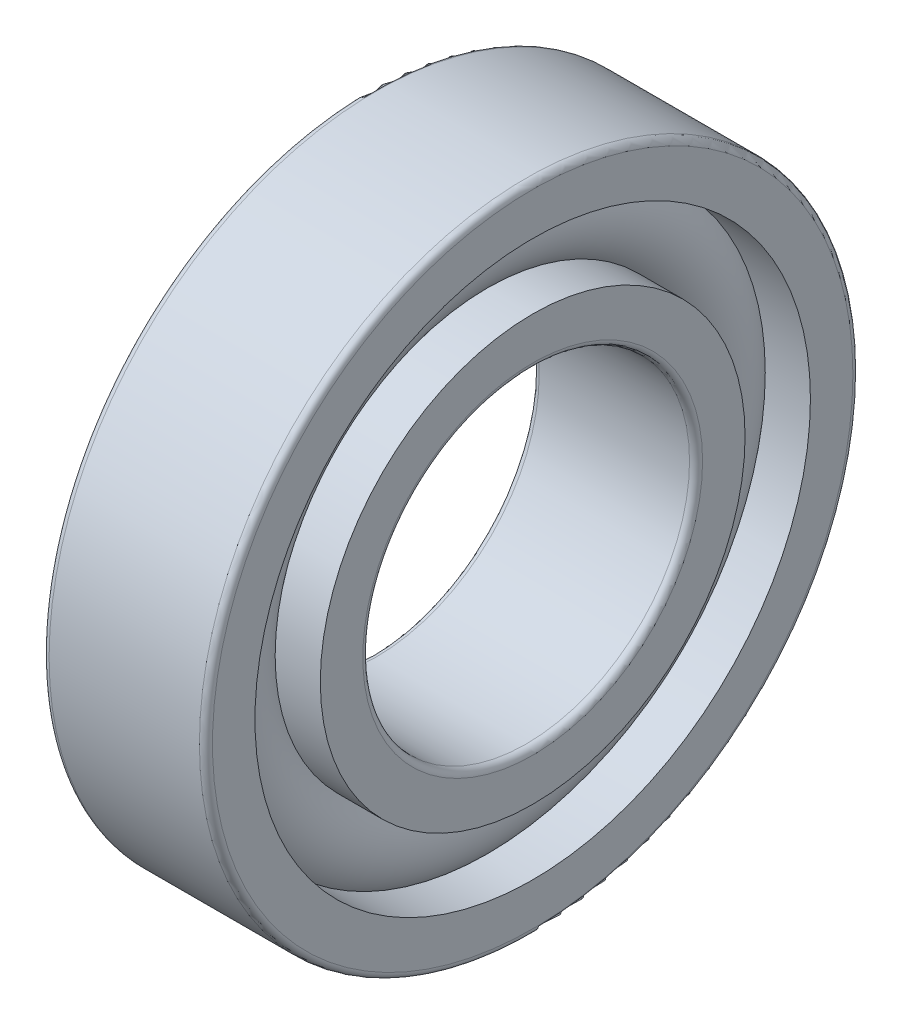
SolidWorks part; units mm, degrees
ref_plane "Plane1" through (0, 0, 0) normal (0, 0, 1) x (1, 0, 0)
ref_plane "Plane2" through (0, 0, 0) normal (0, 1, 0) x (1, 0, 0)
ref_plane "Plane3" through (0, 0, 0) normal (1, 0, 0) x (0, 0, -1)
sketch "Clipboard" plane through (0, 0, 0) normal (0, 0, 1) x (1, 0, 0)
  line L0 (-10, 0) -> (10, 0) construction
  line L1 (0, 0) -> (22.3471, -0.7804)
  line L2 (0, 0) -> (4.7596, 0.1662)
  line L3 (0, 0) -> (22.3471, -0.7804)
  line L4 (0, 0) -> (-22.3573, -0.3902)
  dimension "BallCLRad" = 4.7625
sketch "CagSpiSke" plane through (0, 0, 0) normal (0, 0, 1) x (1, 0, 0)
  line L0 (0.0952, 4.6037) -> (0.0953, 4.9213)
  line L1 (0.0953, 4.9213) -> (-0.0953, 4.9213)
  line L2 (-0.0953, 4.9213) -> (-0.0952, 4.6037)
  line L3 (-0.0952, 4.6037) -> (0.0952, 4.6037)
  line L4 (-20.6375, 0) -> (20.6375, 0) construction
  line L5 (0, 0) -> (0, 23.7692) construction
  dimension "OD" = 9.8425
  dimension "ID" = 9.2075
revolve "CageSpine" add sketch "CagSpiSke" angle 0.001 about L4 reverse direction yes
ref_axis "Axis1" through (-50, 0, 0) along (1, 0, 0)
sketch "CagBalSke" plane through (0, 0, 0) normal (0, 0, 1) x (1, 0, 0)
  line L0 (-1.0477, 4.7625) -> (1.0477, 4.7625)
  line L1 (-1.905, 4.7625) -> (1.905, 4.7625) construction
  line L2 (-10, 0) -> (10, 0) construction
  line L3 (0, 0) -> (0, 24) construction
  arc A0 (1.0477, 4.7625) -> (-1.0477, 4.7625) centre (0, 4.7625) cw
  dimension "BallCLRad" = 4.7625
revolve "CageBall" [suppressed] add sketch "CagBalSke" angle 360 about L1 reverse direction yes
pattern_circular "CageBalls" [suppressed] count 2 every 180 about axis through (-50, 0, 0) along (1, 0, 0)
sketch "CagTrmODSke" plane through (0, 0, 0) normal (0, 0, 1) x (1, 0, 0)
  line L0 (1.0731, 4.9213) -> (1.0732, 5.8357)
  line L1 (1.0732, 5.8357) -> (-1.0732, 5.8357)
  line L2 (-1.0732, 5.8357) -> (-1.0731, 4.9213)
  line L3 (-1.0731, 4.9213) -> (1.0731, 4.9213)
  line L4 (-20.6375, 0) -> (20.6375, 0) construction
  line L5 (0, 0) -> (0, 25) construction
  dimension "Width" = 2.1463
  dimension "ID" = 9.8425
  dimension "OD" = 11.6713
revolve "CageTrimOD" [suppressed] cut sketch "CagTrmODSke" angle 360 about L4 reverse direction yes
sketch "CagTrmIDSke" plane through (0, 0, 0) normal (0, 0, 1) x (1, 0, 0)
  line L0 (1.0732, 3.7401) -> (1.0732, 4.6037)
  line L1 (1.0732, 4.6037) -> (-1.0732, 4.6037)
  line L2 (-1.0732, 4.6037) -> (-1.0732, 3.7401)
  line L3 (-1.0732, 3.7401) -> (1.0732, 3.7401)
  line L4 (-20.6375, 0) -> (20.6375, 0) construction
  line L5 (0, 0) -> (0, 25) construction
  dimension "Width" = 2.1463
  dimension "ID" = 7.4803
  dimension "OD" = 9.2075
revolve "CageTrimID" [suppressed] cut sketch "CagTrmIDSke" angle 360 about L4 reverse direction yes
sketch "BalSimSke" plane through (0, 0, 0) normal (0, 0, 1) x (1, 0, 0)
  line L0 (-10, 0) -> (10, 0) construction
  line L1 (-10, 4.7625) -> (10, 4.7625) construction
  line L2 (0, 0) -> (0, 23) construction
  circle A0 centre (0, 4.7625) radius 0.9525
  dimension "BallCLRad" = 4.7625
  dimension "Ball_diameter" = 1.905
revolve "BallsSimplified" add sketch "BalSimSke" angle 360 about L0
sketch "BalDetSke" plane through (0, 0, 0) normal (0, 0, 1) x (1, 0, 0)
  line L0 (-0.9525, 4.7625) -> (0.9525, 4.7625)
  line L1 (-1.905, 4.7625) -> (1.905, 4.7625) construction
  line L2 (0, 0) -> (0, 25) construction
  arc A0 (0.9525, 4.7625) -> (-0.9525, 4.7625) centre (0, 4.7625) cw
  dimension "BallCLRad" = 4.7625
  dimension "Ball_diameter" = 1.905
revolve "BallDetailed" [suppressed] add sketch "BalDetSke" angle 360 about L1 reverse direction yes
sketch "InnRacSke" plane through (0, 0, 0) normal (0, 0, 1) x (1, 0, 0)
  line L0 (-0.6501, 4.1275) -> (-1.5875, 4.1275)
  line L1 (-1.5875, 4.1275) -> (-1.5875, 3.302)
  line L2 (-1.4605, 3.175) -> (1.4605, 3.175)
  line L3 (1.5875, 3.302) -> (1.5875, 4.1275)
  line L4 (1.5875, 4.1275) -> (0.7009, 4.1275)
  line L5 (-20.6375, 0) -> (20.6375, 0) construction
  line L6 (0, 0) -> (0, 30) construction
  arc A0 (-1.5875, 3.302) -> (-1.4605, 3.175) centre (-1.4605, 3.302) ccw
  arc A1 (1.4605, 3.175) -> (1.5875, 3.302) centre (1.4605, 3.302) ccw
  arc A2 (0.7009, 4.1275) -> (-0.6501, 4.1275) centre (0.0254, 4.7625) cw
  dimension "BallCLRad" = 4.7625
  dimension "Fillet_radius" = 0.127
  dimension "Ball_diameter" = 1.8542
  dimension "ID" = 6.35
  dimension "OD" = 8.255
  dimension "Width" = 3.175
revolve "InnerRace" add sketch "InnRacSke" angle 360 about L5 reverse direction yes
sketch "OutRacSke" plane through (0, 0, 0) normal (0, 0, 1) x (1, 0, 0)
  line L0 (-0.6755, 5.3975) -> (-1.5875, 5.3975)
  line L1 (-1.5875, 5.3975) -> (-1.5875, 6.223)
  line L2 (-1.4605, 6.35) -> (1.4605, 6.35)
  line L3 (1.5875, 6.223) -> (1.5875, 5.3975)
  line L4 (1.5875, 5.3975) -> (0.6755, 5.3975)
  line L5 (-20.6375, 0) -> (20.6375, 0) construction
  line L6 (0, 0) -> (0, 30) construction
  arc A0 (-1.5875, 6.223) -> (-1.4605, 6.35) centre (-1.4605, 6.223) cw
  arc A1 (1.4605, 6.35) -> (1.5875, 6.223) centre (1.4605, 6.223) cw
  arc A2 (0.6755, 5.3975) -> (-0.6755, 5.3975) centre (0, 4.7625) ccw
  dimension "BallCLRad" = 4.7625
  dimension "Fillet_radius" = 0.127
  dimension "Ball_diameter" = 1.8542
  dimension "Width" = 3.175
revolve "OuterRace" add sketch "OutRacSke" angle 360 about L5 reverse direction yes
pattern_circular "BallsDetailed" [suppressed] count 2 every 180 about axis through (-50, 0, 0) along (1, 0, 0)
equation "\"BallCLRad@Clipboard\" = ( \"OD@OutRacSke\" + \"ID@InnRacSke\" ) / 4"
equation "\"BallCLRad@BalSimSke\" = \"BallCLRad@Clipboard\""
equation "\"BallCLRad@BalDetSke\" = \"BallCLRad@Clipboard\""
equation "\"BallCLRad@InnRacSke\" = \"BallCLRad@Clipboard\""
equation "\"BallCLRad@OutRacSke\" = \"BallCLRad@Clipboard\""
equation "\"Ball_diameter@InnRacSke\" = \"Ball_diameter@BalDetSke\" - 0.002"
equation "\"Ball_diameter@OutRacSke\" = \"Ball_diameter@BalDetSke\" - 0.002"
equation "\"Ball_diameter@BalSimSke\" = \"Ball_diameter@BalDetSke\""
equation "\"Width@OutRacSke\" = \"Width@InnRacSke\""
equation "\"Fillet_radius@OutRacSke\" = \"Fillet_radius@InnRacSke\""
equation "\"Max_count@Clipboard\" = int( 3.14159265 / atn(( \"Ball_diameter@BalDetSke\" / 2) / sqr( \"BallCLRad@Clipboard\"  *  \"BallCLRad@Clipboard\" - ( \"Ball_diameter@BalDetSke\" / 2) *  ( \"Ball_diameter@BalDetSke\" / 2))))"
equation "\"Max_count@Clipboard\" = ((sgn( \"Max_count@Clipboard\" - \"Count@Clipboard\" )-1)*( \"Max_count@Clipboard\" - \"Count@Clipboard\" ))/-2+ \"Count@Clipboard\""
equation "\"Count@BallsDetailed\" = int( \"Show_count@Clipboard\" ) "
equation "\"Count@BallsDetailed\" = ((sgn( \"Count@BallsDetailed\" - \"Max_count@Clipboard\" )-1)*( \"Count@BallsDetailed\" - \"Max_count@Clipboard\" ))/-2+ \"Max_count@Clipboard\""
equation "\"Count@BallsDetailed\" = ((sgn( \"Count@BallsDetailed\" - \"Min_count@Clipboard\" )+1)*( \"Count@BallsDetailed\" - \"Min_count@Clipboard\"))/2 +\"Min_count@Clipboard\""
equation "\"Angle@BallsDetailed\" = 360.0 / \"Max_count@Clipboard\""
equation "\"BallCLRad@CagBalSke\" = \"BallCLRad@Clipboard\""
equation "\"Count@CageBalls\" = \"Count@BallsDetailed\""
equation "\"Angle@CageBalls\" = \"Angle@BallsDetailed\""
equation "\"Angle@CageSpine\" =  \"Angle@CageBalls\" * ( \"Count@CageBalls\" -1 + int( \"Count@CageBalls\" / \"Max_count@Clipboard\" ) )  + 0.001 -  int( \"Count@CageBalls\" / \"Max_count@Clipboard\" ) * 0.001"
equation "\"Angle@CageSpine\" =  \"Angle@CageSpine\" * int( \"Min_count@Clipboard\" / 2) + int(1 / \"Min_count@Clipboard\")  * 0.001"
equation "\"CageWallOD@CagBalSke\" =  \"Ball_diameter@BalDetSke\" * 1.1"
equation "\"Thickness@CagSpiSke\" =  \"Ball_diameter@BalDetSke\" * 0.1"
equation "\"OD@CagTrmODSke\" = \"BallCLRad@Clipboard\" * 2 + \"CageWallOD@CagBalSke\" + 0.002"
equation "\"ID@CagTrmODSke\" = \"BallCLRad@Clipboard\" * 2 + \"Ball_diameter@BalDetSke\" / 6"
equation "\"OD@CagTrmIDSke\" = \"BallCLRad@Clipboard\" * 2 - \"Ball_diameter@BalDetSke\" / 6"
equation "\"ID@CagTrmIDSke\" = \"BallCLRad@Clipboard\" * 2 - \"CageWallOD@CagBalSke\" + 0.002"
equation "\"OD@CagSpiSke\" = \"ID@CagTrmODSke\""
equation "\"ID@CagSpiSke\" = \"OD@CagTrmIDSke\""
equation "\"Width@CagTrmODSke\" = \"CageWallOD@CagBalSke\" + 0.002"
equation "\"Width@CagTrmIDSke\" = \"CageWallOD@CagBalSke\" + 0.002"
